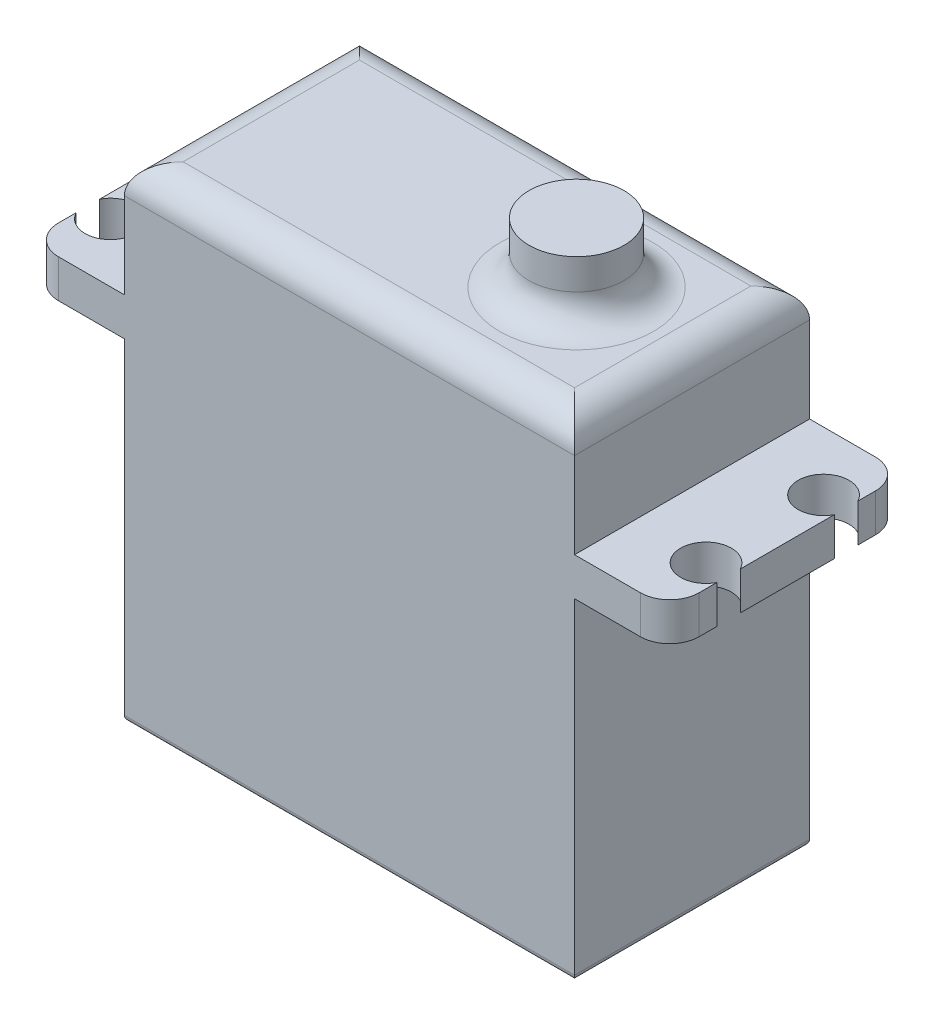
SolidWorks part; units mm, degrees
ref_plane "前视基准面" through (0, 0, 0) normal (0, 0, 1) x (1, 0, 0)
ref_plane "上视基准面" through (0, 0, 0) normal (0, 1, 0) x (1, 0, 0)
ref_plane "右视基准面" through (0, 0, 0) normal (1, 0, 0) x (0, 0, -1)
sketch "Sketch1" plane through (0, 0, 0) normal (0, 1, 0) x (1, 0, 0)
  line L0 (-29.6646, 8.16) -> (-29.6646, -11.94) construction
  line L1 (-29.6646, 8.16) -> (-29.6646, -11.78) construction
  line L14 (-19.15, 10) -> (-19.15, -10)
  line L15 (-24.75, 10) -> (24.75, 10)
  line L16 (-27.25, 7.5) -> (-27.25, 6)
  line L17 (-24.75, -10) -> (24.75, -10)
  line L18 (27.25, 7.5) -> (27.25, 6)
  line L19 (27.25, -6) -> (27.25, -7.5)
  line L20 (19.15, 10) -> (19.15, -10)
  line L21 (27.25, 4) -> (27.25, -4)
  line L22 (-27.25, -6) -> (-27.25, -7.5)
  line L23 (-27.25, 4) -> (-27.25, -4)
  line L25 (-19.15, 10) -> (19.15, 10)
  line L26 (-19.15, 10) -> (-19.15, -10)
  line L27 (-19.15, -10) -> (19.15, -10)
  line L28 (19.15, 10) -> (19.15, -10)
  arc A1 (27.25, 6) -> (27.25, 4) centre (25.3354, 5) ccw
  arc A9 (27.25, -4) -> (27.25, -6) centre (25.3354, -5) ccw
  arc A10 (27.25, 7.5) -> (24.75, 10) centre (24.75, 7.5) ccw
  arc A11 (24.75, -10) -> (27.25, -7.5) centre (24.75, -7.5) ccw
  arc A12 (-24.75, -10) -> (-27.25, -7.5) centre (-24.75, -7.5) cw
  arc A13 (-24.75, 10) -> (-27.25, 7.5) centre (-24.75, 7.5) ccw
  arc A14 (-27.25, 6) -> (-27.25, 4) centre (-25.3354, 5) cw
  arc A15 (-27.25, -4) -> (-27.25, -6) centre (-25.3354, -5) cw
  point P6 (-23.0194, 35.6443)
  point P7 (-28.2176, 31.4543)
  point P12 (-23.0194, 35.6443)
  point P61 (27.25, 10)
  point P64 (27.25, -10)
  point P69 (-27.25, 10)
  dimension "D4" = 10
  dimension "D18" = 54.5
  dimension "D22" = 2.16
  dimension "D25" = 5
  dimension "D27" = 2.16
  dimension "D28" = 2.5
  dimension "D29" = 2.5
  dimension "D30" = 2.5
  dimension "D31" = 2.5
  dimension "D32" = 2.16
  dimension "D35" = 2.16
  dimension "D5" = 27.25
  dimension "D19" = 20
  dimension "D20" = 8.1
  dimension "D21" = 8.1
  dimension "D23" = 2
  dimension "D24" = 5
  dimension "D26" = 10
  dimension "D33" = 2
  dimension "D34" = 5
  dimension "D36" = 2
  dimension "D37" = 10
extrude "Boss-Extrude2" add sketch "Sketch1" along normal blind 3.24 contours L23 A15 L22 A12 L17 L14 L15 A13 L16 A14 | L17 A11 L19 A9 L21 A1 L18 A10 L15 L20 region at (-22.6703, 0, 0) region at (22.6703, 0, 0)
extrude "Boss-Extrude3" add sketch "Sketch1<9>" along normal blind 13.04 contours L20 L15 L14 L17 region at (0, 0, 0)
sketch "Sketch1<9>" plane through (0, 0, 0) normal (0, 1, 0) x (1, 0, 0) same geometry as "Sketch1"
sketch "Sketch2" plane through (0, 13.04, 0) normal (0, 1, 0) x (1, 0, 0)
  circle A0 centre (9.32, 0) radius 4.04
  point P2 (0, 0)
  dimension "D1" = 8.08
  dimension "D2" = 9.32
extrude "Boss-Extrude4" add sketch "Sketch2" along normal blind 5.1
sketch "Sketch3" plane through (0, 18.14, 0) normal (0, 1, 0) x (1, 0, 0)
  line L0 (-19.15, 10) -> (19.15, 10) construction
  line L1 (19.15, 10) -> (19.15, -10) construction
  line L2 (2.5427, 8.1594) -> (-1.7714, 1.5822)
  line L3 (3.255, 3.8667) -> (0.7882, 5.4846)
  circle A0 centre (9.15, 0) radius 10
  circle A1 centre (9.15, 0) radius 1.48
  circle A2 centre (3.255, 3.8667) radius 1.17
  circle A7 centre (13.0167, 5.895) radius 1.17
  circle A8 centre (15.045, -3.8667) radius 1.17
  circle A9 centre (5.2833, -5.895) radius 1.17
  point P9 (0.7882, 5.4846)
  point P12 (0.7882, 5.4846)
  point P14 (0.7882, 5.4846)
  point P15 (0.7882, 5.4846)
  point P16 (0.7882, 5.4846)
  point P26 (9.15, 0)
  dimension "D1" = 20
  dimension "D2" = 2.96
  dimension "D3" = 2.34
  dimension "D4" = 7.05
  dimension "D5" = 2.34
  dimension "D8" = 4
extrude "Boss-Extrude7" add sketch "Sketch1<10>" against normal blind 16.74 contours L20 L15 L14 L17 region at (0, 0, 0)
sketch "Sketch1<10>" plane through (0, 0, 0) normal (0, 1, 0) x (1, 0, 0) same geometry as "Sketch1"
sketch "Sketch5" plane through (0, -16.74, 0) normal (0, -1, 0) x (1, 0, 0)
  line L1 (-19.15, 10) -> (19.15, 10)
  line L2 (-19.15, 10) -> (-19.15, -10)
  line L3 (-19.15, -10) -> (19.15, -10)
  line L4 (19.15, 10) -> (19.15, -10)
extrude "Boss-Extrude8" add sketch "Sketch5" along normal blind 11.5
fillet "Fillet1" radius 2.5 5 edges at (0, 13.04, 10) (-19.15, 13.04, 0) (0, 13.04, -10) (19.15, 13.04, 0) (9.32, 13.04, 4.04)
fillet "Fillet2" radius 0.5 4 edges at (0, -28.24, 10) (19.15, -28.24, 0) (0, -28.24, -10) (-19.15, -28.24, 0)
sketch "Sketch6" plane through (0, -28.24, 0) normal (0, -1, 0) x (1, 0, 0)
  line L0 (-18.65, 5.04) -> (-16.22, 5.04)
  line L1 (-14.19, 7.07) -> (-14.19, 9.5)
  line L2 (14.19, 9) -> (18.25, 9) construction
  line L3 (-18.25, -4.1344) -> (-18.25, -8.3924) construction
  line L4 (-18.65, 9.5) -> (-18.65, -9.5) construction
  line L5 (-18.25, -9.1) -> (-12.8842, -9.1) construction
  line L6 (-18.65, -9.5) -> (18.65, -9.5) construction
  line L7 (-18.65, -5.04) -> (-16.22, -5.04)
  line L8 (-14.19, -7.07) -> (-14.19, -9.5)
  line L9 (-18.1107, 9.1) -> (-14.19, 9.1) construction
  line L10 (-18.25, 9.1) -> (-18.25, 5.04) construction
  line L11 (18.65, 9.5) -> (-18.65, 9.5) construction
  line L12 (18.25, 9) -> (18.25, 4.94) construction
  line L13 (18.65, -9.5) -> (18.65, 9.5) construction
  line L14 (18.65, 4.94) -> (16.22, 4.94)
  line L15 (14.19, 6.97) -> (14.19, 9.5)
  line L16 (18.25, -5.04) -> (18.25, -9.1) construction
  line L17 (18.25, -9.1) -> (13.9341, -9.1) construction
  line L18 (14.19, -9.5) -> (14.19, -7.07)
  line L19 (16.22, -5.04) -> (18.65, -5.04)
  circle A0 centre (-16.22, 7.07) radius 2.03
  circle A1 centre (-16.22, -7.07) radius 2.03
  circle A2 centre (16.22, 6.97) radius 2.03
  circle A3 centre (16.22, -7.07) radius 2.03
  line M1 (18.65, -9.5) -> (18.65, 9.5)
  line M2 (18.65, 9.5) -> (-18.65, 9.5)
  line M3 (-18.65, 9.5) -> (-18.65, -9.5)
  line M4 (-18.65, -9.5) -> (18.65, -9.5)
  dimension "D1" = 4.06
  dimension "D2" = 4.06
  dimension "D6" = 0.4
  dimension "D7" = 4.06
  dimension "D10" = 0.4
  dimension "D11" = 4.06
  dimension "D3" = 0.4
  dimension "D4" = 0.4
  dimension "D5" = 0.4
  dimension "D8" = 0.5
  dimension "D9" = 0.4
extrude "Cut-Extrude1" cut sketch "Sketch6" against normal blind 1.66 contours A0 | A0 L1 L0 M2 M3 | A1 | A1 L7 L8 M3 M4 | A2 | A2 L14 L15 M1 M2 | A3 | A3 L18 L19 M4 M1 | A0 region at (-18.5869, -28.24, 7.27) region at (-16.22, -28.24, 7.07) region at (-17.435, -28.24, -5.1031) region at (-16.22, -28.24, -7.07) region at (16.42, -28.24, 9.4362) region at (16.22, -28.24, 6.97) region at (14.2531, -28.24, -8.285) region at (16.22, -28.24, -7.07)
